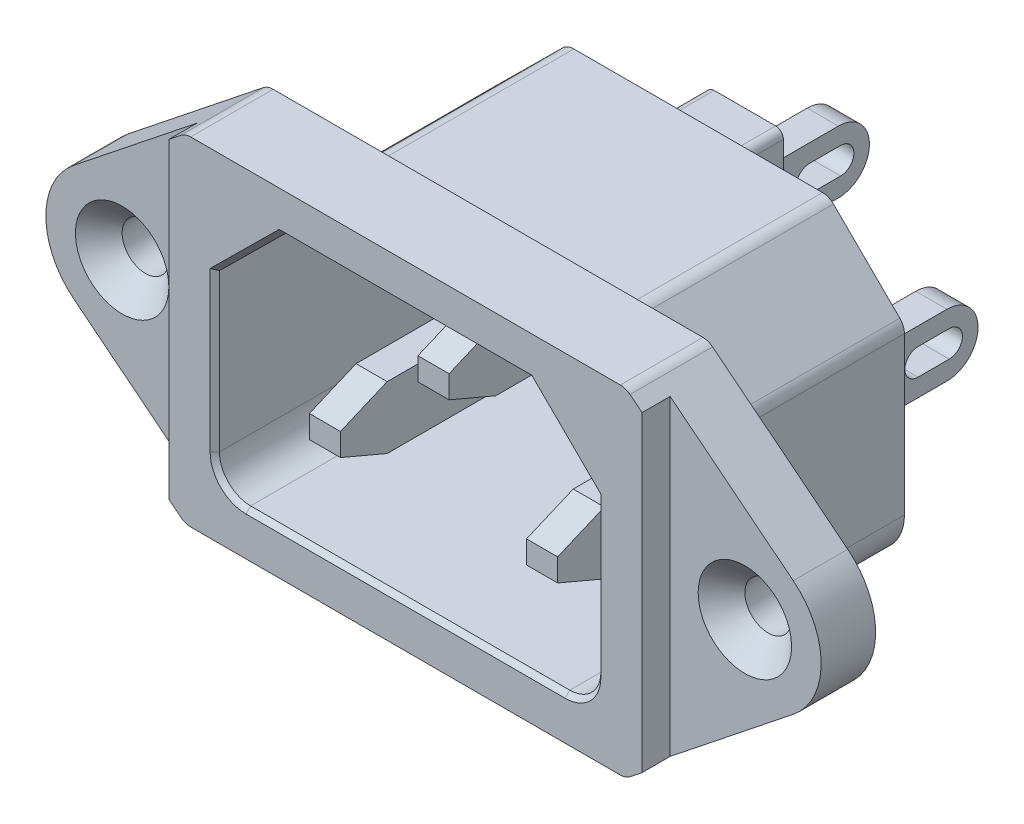
SolidWorks part; units mm, degrees
material "PVC Rigid"
ref_plane "Front Plane" through (0, 0, 0) normal (0, 0, 1) x (1, 0, 0)
ref_plane "Top Plane" through (0, 0, 0) normal (0, 1, 0) x (1, 0, 0)
ref_plane "Right Plane" through (0, 0, 0) normal (1, 0, 0) x (0, 0, -1)
sketch "Sketch1" plane through (0, 0, 0) normal (0, 0, 1) x (1, 0, 0)
  line L0 (1.791, 3.7158) -> (10.4766, 10.6323)
  line L1 (11.0995, 10.85) -> (38.7005, 10.85)
  line L2 (39.3234, 10.6323) -> (48.009, 3.7158)
  line L3 (48.009, -3.7158) -> (39.3234, -10.6323)
  line L4 (38.7005, -10.85) -> (11.0995, -10.85)
  line L5 (10.4766, -10.6323) -> (1.791, -3.7158)
  line L6 (4.75, 0) -> (45.05, 0) construction
  line L7 (24.9, 10.85) -> (24.9, -10.85) construction
  arc A0 (48.009, 3.7158) -> (48.009, -3.7158) centre (45.05, 0) cw
  arc A1 (1.791, 3.7158) -> (1.791, -3.7158) centre (4.75, 0) ccw
  arc A2 (11.0995, -10.85) -> (10.4766, -10.6323) centre (11.0995, -9.85) cw
  arc A3 (39.3234, -10.6323) -> (38.7005, -10.85) centre (38.7005, -9.85) cw
  arc A4 (38.7005, 10.85) -> (39.3234, 10.6323) centre (38.7005, 9.85) cw
  arc A5 (10.4766, 10.6323) -> (11.0995, 10.85) centre (11.0995, 9.85) cw
  circle A6 centre (4.9, 0) radius 1.5
  circle A7 centre (44.9, 0) radius 1.5
  point P12 (0, 0)
  point P13 (49.8, 0)
  point P21 (39.05, 10.85)
  point P24 (10.75, 10.85)
  point P29 (0, 0)
  point P30 (0, 0)
  dimension "D1" = 4.75
  dimension "D5" = 1
  dimension "D6" = 40
  dimension "D7" = 3
  dimension "D2" = 49.8
  dimension "D3" = 21.7
  dimension "D4" = 28.3
extrude "Boss-Extrude1" add sketch "Sketch1" along normal blind 21.8
sketch "Sketch2" plane through (0, 0, 21.8) normal (0, 0, 1) x (1, 0, 0)
  line L0 (11.0995, -10.85) -> (38.7005, -10.85) construction
  line L1 (11.0995, -10.85) -> (38.7005, -10.85)
  line L2 (9.7, -10.0139) -> (9.7, 10.0139)
  line L3 (11.0995, 10.85) -> (38.7005, 10.85)
  line L4 (40.1, -10.0139) -> (40.1, 10.0139)
  line L6 (24.9, -10.85) -> (24.9, -2.6264) construction
  line L7 (48.009, 3.7158) -> (39.3234, 10.6323) construction
  line L8 (39.3234, -10.6323) -> (48.009, -3.7158) construction
  line L9 (1.791, -3.7158) -> (10.4766, -10.6323) construction
  line L10 (10.4766, 10.6323) -> (1.791, 3.7158) construction
  line L11 (40.1, 10.0139) -> (39.3234, 10.6323)
  line L12 (39.3234, -10.6323) -> (40.1, -10.0139)
  line L13 (9.7, -10.0139) -> (10.4766, -10.6323)
  line L14 (10.4766, 10.6323) -> (9.7, 10.0139)
  line L16 (-4.1169, -19.3982) -> (50.7137, -19.3982)
  line L17 (-4.1169, -19.3982) -> (-4.1169, 12.7876)
  line L18 (-4.1169, 12.7876) -> (50.7137, 12.7876)
  line L19 (50.7137, -19.3982) -> (50.7137, 12.7876)
  arc A0 (39.3234, 10.6323) -> (38.7005, 10.85) centre (38.7005, 9.85) ccw construction
  arc A1 (38.7005, -10.85) -> (39.3234, -10.6323) centre (38.7005, -9.85) ccw construction
  arc A2 (10.4766, -10.6323) -> (11.0995, -10.85) centre (11.0995, -9.85) ccw construction
  arc A3 (11.0995, 10.85) -> (10.4766, 10.6323) centre (11.0995, 9.85) ccw construction
  arc A4 (39.3234, 10.6323) -> (38.7005, 10.85) centre (38.7005, 9.85) ccw
  arc A5 (38.7005, -10.85) -> (39.3234, -10.6323) centre (38.7005, -9.85) ccw
  arc A6 (10.4766, -10.6323) -> (11.0995, -10.85) centre (11.0995, -9.85) ccw
  arc A7 (11.0995, 10.85) -> (10.4766, 10.6323) centre (11.0995, 9.85) ccw
extrude "Cut-Extrude1" cut sketch "Sketch2" against normal blind 1.8
sketch "Sketch3" plane through (0, 0, 0) normal (0, 0, -1) x (-1, 0, 0)
  line L0 (-38.15, -9.05) -> (-38.15, 4.45)
  line L1 (-38.15, 4.45) -> (-33.3, 9.25)
  line L2 (-33.3, 9.25) -> (-16.5, 9.25)
  line L3 (-16.5, 9.25) -> (-11.65, 4.45)
  line L4 (-11.65, 4.45) -> (-11.65, -9.05)
  line L5 (-11.65, -9.05) -> (-38.15, -9.05)
  line L6 (-11.0995, -10.85) -> (-38.7005, -10.85) construction
  line L7 (-24.9, 9.25) -> (-24.9, -9.05) construction
  line L9 (-53.6764, -18.0994) -> (4.0477, -18.0994)
  line L10 (-53.6764, -18.0994) -> (-53.6764, 14.6166)
  line L11 (-53.6764, 14.6166) -> (4.0477, 14.6166)
  line L12 (4.0477, -18.0994) -> (4.0477, 14.6166)
  point P2 (-24.9, -10.85)
  point P7 (-24.9, -9.05)
  dimension "D1" = 26.5
  dimension "D2" = 18.3
  dimension "D3" = 1.8
  dimension "D4" = 16.8
  dimension "D5" = 13.5
extrude "Cut-Extrude2" cut sketch "Sketch3" against normal blind 16.5
fillet "Fillet1" radius 3 2 edges at (11.65, -9.05, 8.25) (38.15, -9.05, 8.25)
fillet "Fillet2" radius 1 4 edges at (38.15, 4.45, 8.25) (33.3, 9.25, 8.25) (16.5, 9.25, 8.25) (11.65, 4.45, 8.25)
sketch "Sketch4" plane through (0, 0, 21.8) normal (0, 0, 1) x (1, 0, 0)
  line L12 (37.15, 4.0327) -> (32.8888, 8.25)
  line L13 (37.15, -6.05) -> (37.15, 4.0327)
  line L14 (14.65, -8.05) -> (35.15, -8.05)
  line L15 (12.65, 4.0327) -> (12.65, -6.05)
  line L16 (16.9112, 8.25) -> (12.65, 4.0327)
  line L17 (32.8888, 8.25) -> (16.9112, 8.25)
  line L18 (37.15, 4.0327) -> (32.8888, 8.25)
  line L19 (37.15, -6.05) -> (37.15, 4.0327)
  line L20 (14.65, -8.05) -> (35.15, -8.05)
  line L21 (12.65, 4.0327) -> (12.65, -6.05)
  line L22 (16.9112, 8.25) -> (12.65, 4.0327)
  line L23 (32.8888, 8.25) -> (16.9112, 8.25)
  arc A12 (35.15, -8.05) -> (37.15, -6.05) centre (35.15, -6.05) ccw
  arc A13 (12.65, -6.05) -> (14.65, -8.05) centre (14.65, -6.05) ccw
  arc A14 (35.15, -8.05) -> (37.15, -6.05) centre (35.15, -6.05) ccw
  arc A15 (12.65, -6.05) -> (14.65, -8.05) centre (14.65, -6.05) ccw
  dimension "D1" = 1
extrude "Cut-Extrude3" cut sketch "Sketch4" against normal blind 17.8
chamfer "Chamfer1" distance 0.3 angle 45 8 edges at (37.15, -1.0086, 21.8) (36.5642, -7.4642, 21.8) (24.9, -8.05, 21.8) (13.2358, -7.4642, 21.8) (35.0194, 6.1414, 21.8) (12.65, -1.0086, 21.8) (14.7806, 6.1414, 21.8) (24.9, 8.25, 21.8)
chamfer "Chamfer2" distance 1.5 angle 45 2 edges at (3.4, 0, 20) (43.4, 0, 20)
sketch "Sketch5" plane through (0, 0, 0) normal (0, 0, -1) x (-1, 0, 0)
  line L1 (-26.875, -1.55) -> (-22.925, -1.55)
  line L2 (-27.375, -1.05) -> (-27.375, 7.95)
  line L3 (-26.875, 8.45) -> (-22.925, 8.45)
  line L4 (-22.425, -1.05) -> (-22.425, 7.95)
  line L5 (-19.9, -8.25) -> (-15.95, -8.25)
  line L6 (-20.4, -7.75) -> (-20.4, 1.25)
  line L7 (-19.9, 1.75) -> (-15.95, 1.75)
  line L8 (-15.45, -7.75) -> (-15.45, 1.25)
  line L9 (-33.85, -8.25) -> (-29.9, -8.25)
  line L10 (-34.35, -7.75) -> (-34.35, 1.25)
  line L11 (-33.85, 1.75) -> (-29.9, 1.75)
  line L12 (-29.4, -7.75) -> (-29.4, 1.25)
  line L14 (-35.15, -9.05) -> (-14.65, -9.05) construction
  line L15 (-16.9112, 9.25) -> (-32.8888, 9.25) construction
  line L16 (-40.7756, -11.3531) -> (-7.6971, -11.3531)
  line L17 (-40.7756, -11.3531) -> (-40.7756, 11.239)
  line L18 (-40.7756, 11.239) -> (-7.6971, 11.239)
  line L19 (-7.6971, -11.3531) -> (-7.6971, 11.239)
  arc A0 (-29.9, -8.25) -> (-29.4, -7.75) centre (-29.9, -7.75) ccw
  arc A1 (-34.35, 1.25) -> (-33.85, 1.75) centre (-33.85, 1.25) cw
  arc A2 (-29.9, 1.75) -> (-29.4, 1.25) centre (-29.9, 1.25) cw
  arc A3 (-33.85, -8.25) -> (-34.35, -7.75) centre (-33.85, -7.75) cw
  arc A4 (-15.95, -8.25) -> (-15.45, -7.75) centre (-15.95, -7.75) ccw
  arc A5 (-20.4, 1.25) -> (-19.9, 1.75) centre (-19.9, 1.25) cw
  arc A6 (-15.95, 1.75) -> (-15.45, 1.25) centre (-15.95, 1.25) cw
  arc A7 (-19.9, -8.25) -> (-20.4, -7.75) centre (-19.9, -7.75) cw
  arc A8 (-22.925, -1.55) -> (-22.425, -1.05) centre (-22.925, -1.05) ccw
  arc A9 (-27.375, 7.95) -> (-26.875, 8.45) centre (-26.875, 7.95) cw
  arc A10 (-22.925, 8.45) -> (-22.425, 7.95) centre (-22.925, 7.95) cw
  arc A11 (-26.875, -1.55) -> (-27.375, -1.05) centre (-26.875, -1.05) cw
  point P36 (-22.425, -1.55)
  point P39 (-27.375, 8.45)
  point P42 (-22.425, 8.45)
  dimension "D6" = 0.5
  dimension "D1" = 10
  dimension "D2" = 4.95
  dimension "D3" = 0.8
  dimension "D4" = 0.8
  dimension "D5" = 9
extrude "Cut-Extrude4" cut sketch "Sketch5" against normal blind 3
sketch "Sketch6" plane through (0, 0, 20) normal (0, 0, 1) x (1, 0, 0)
  line L1 (23.9, 1.45) -> (25.9, 1.45)
  line L2 (23.9, 1.45) -> (23.9, 5.45)
  line L3 (23.9, 5.45) -> (25.9, 5.45)
  line L4 (25.9, 1.45) -> (25.9, 5.45)
  line L5 (16.925, -5.25) -> (18.925, -5.25)
  line L6 (16.925, -5.25) -> (16.925, -1.25)
  line L7 (16.925, -1.25) -> (18.925, -1.25)
  line L8 (18.925, -5.25) -> (18.925, -1.25)
  line L9 (30.875, -5.25) -> (32.875, -5.25)
  line L10 (30.875, -5.25) -> (30.875, -1.25)
  line L11 (30.875, -1.25) -> (32.875, -1.25)
  line L12 (32.875, -5.25) -> (32.875, -1.25)
  line L13 (27.375, 7.95) -> (27.375, -1.05) construction
  line L14 (26.875, -1.55) -> (22.925, -1.55) construction
  line L15 (20.4, 1.25) -> (20.4, -7.75) construction
  line L16 (15.95, 1.75) -> (19.9, 1.75) construction
  line L17 (29.9, 1.75) -> (33.85, 1.75) construction
  line L18 (34.35, 1.25) -> (34.35, -7.75) construction
  point P12 (24.9, 1.45)
  point P13 (25.9, 3.45)
  point P14 (27.375, 3.45)
  point P15 (24.9, -1.55)
  point P18 (20.4, -3.25)
  point P21 (17.925, 1.75)
  point P22 (18.925, -3.25)
  point P25 (31.875, 1.75)
  point P28 (34.35, -3.25)
  point P31 (32.875, -3.25)
  point P34 (31.875, -1.25)
  point P35 (0, 0)
  point P36 (17.925, -1.25)
  point P37 (0, 0)
  point P38 (0, 0)
  dimension "D1" = 4
  dimension "D2" = 2
extrude "Boss-Extrude2" add sketch "Sketch6" against normal blind 27
chamfer "Chamfer3" distance 3 angle 23 6 edges at (31.875, -5.25, 20) (31.875, -1.25, 20) (17.925, -5.25, 20) (17.925, -1.25, 20) (24.9, 1.45, 20) (24.9, 5.45, 20) first distance on face at (31.875, -5.25, 12) first distance on face at (31.875, -1.25, 12) first distance on face at (17.925, -5.25, 12) first distance on face at (17.925, -1.25, 12) first distance on face at (24.9, 1.45, 12) first distance on face at (24.9, 5.45, 12)
sketch "Sketch7" plane through (25.9, 0, 0) normal (1, 0, 0) x (0, 0, -1)
  line L0 (3.15, 3.45) -> (5.15, 3.45) construction
  line L1 (3.15, 4.3) -> (5.15, 4.3)
  line L2 (3.15, 2.6) -> (5.15, 2.6)
  line L3 (3.15, -3.25) -> (5.15, -3.25) construction
  line L4 (3.15, -2.4) -> (5.15, -2.4)
  line L5 (3.15, -4.1) -> (5.15, -4.1)
  line L6 (7, 1.45) -> (7, 5.45) construction
  line L7 (7, -5.25) -> (7, -1.25) construction
  arc A0 (3.15, 4.3) -> (3.15, 2.6) centre (3.15, 3.45) ccw
  arc A1 (5.15, 2.6) -> (5.15, 4.3) centre (5.15, 3.45) ccw
  arc A2 (3.15, -2.4) -> (3.15, -4.1) centre (3.15, -3.25) ccw
  arc A3 (5.15, -4.1) -> (5.15, -2.4) centre (5.15, -3.25) ccw
  point P2 (4.15, 3.45)
  point P7 (4.15, -3.25)
  point P14 (7, -3.25)
  point P15 (7, 3.45)
  point P16 (6, -3.25)
  point P21 (6, 3.45)
  point P22 (0, 0)
  point P23 (0, 0)
  dimension "D1" = 0.85
  dimension "D2" = 1
  dimension "D3" = 2
extrude "Cut-Extrude5" cut sketch "Sketch7" against normal through all both and the other way through all
fillet "Fillet3" radius 2 6 edges at (31.875, -5.25, -7) (31.875, -1.25, -7) (17.925, -5.25, -7) (24.9, 1.45, -7) (17.925, -1.25, -7) (24.9, 5.45, -7)
